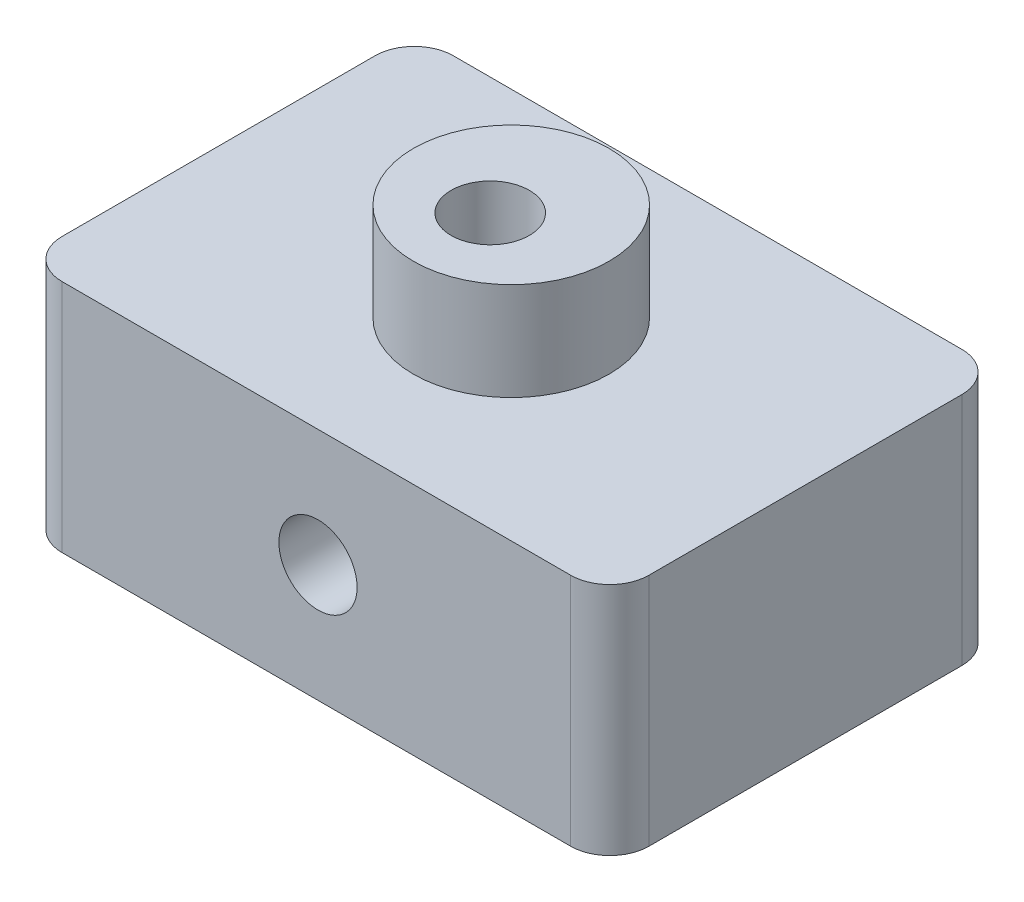
SolidWorks part; units mm, degrees
ref_plane "Спереди" through (0, 0, 0) normal (0, 0, 1) x (1, 0, 0)
ref_plane "Сверху" through (0, 0, 0) normal (0, 1, 0) x (1, 0, 0)
ref_plane "Справа" through (0, 0, 0) normal (1, 0, 0) x (0, 0, -1)
sketch "Эскиз1" plane through (0, 0, 0) normal (0, 1, 0) x (1, 0, 0)
  line L1 (-75.4062, 50.6016) -> (74.5938, 50.6016)
  line L2 (-75.4062, 50.6016) -> (-75.4062, -49.3984)
  line L3 (-75.4062, -49.3984) -> (74.5938, -49.3984)
  line L4 (74.5938, 50.6016) -> (74.5938, -49.3984)
  dimension "D1" = 150
  dimension "D2" = 100
extrude "Вытянуть1" add sketch "Эскиз1" along normal blind 30 and the other way blind 30
fillet "Скругление1" radius 10 1 edges at (-75.4062, 0, -50.6016)
fillet "Скругление2" radius 10 3 edges at (-75.4062, 0, 49.3984) (74.5938, 0, 49.3984) (74.5938, 0, -50.6016)
sketch "Эскиз2" plane through (0, 30, 0) normal (0, 1, 0) x (1, 0, 0)
  circle A0 centre (0, 0) radius 25
  dimension "D1" = 50
extrude "Вытянуть2" add sketch "Эскиз2" along normal blind 25
sketch "Эскиз3" plane through (0, 55, 0) normal (0, 1, 0) x (1, 0, 0)
  circle A0 centre (0, 0) radius 15
  dimension "D1" = 30
extrude "Вырез-Вытянуть1" [suppressed] cut sketch "Эскиз3" against normal through all
sketch "Sketch3" plane through (0, 0, 49.3984) normal (0, 0, 1) x (1, 0, 0)
  circle A0 centre (0, 0) radius 10
  dimension "D1" = 20
extrude "Cut-Extrude1" cut sketch "Sketch3" against normal through all contours A0
sketch "Sketch4" plane through (0, 55, 0) normal (0, 1, 0) x (1, 0, 0)
  circle A0 centre (-0.899, -4.4682) radius 10
  dimension "D1" = 20
extrude "Cut-Extrude2" cut sketch "Sketch4" against normal through all contours A0
